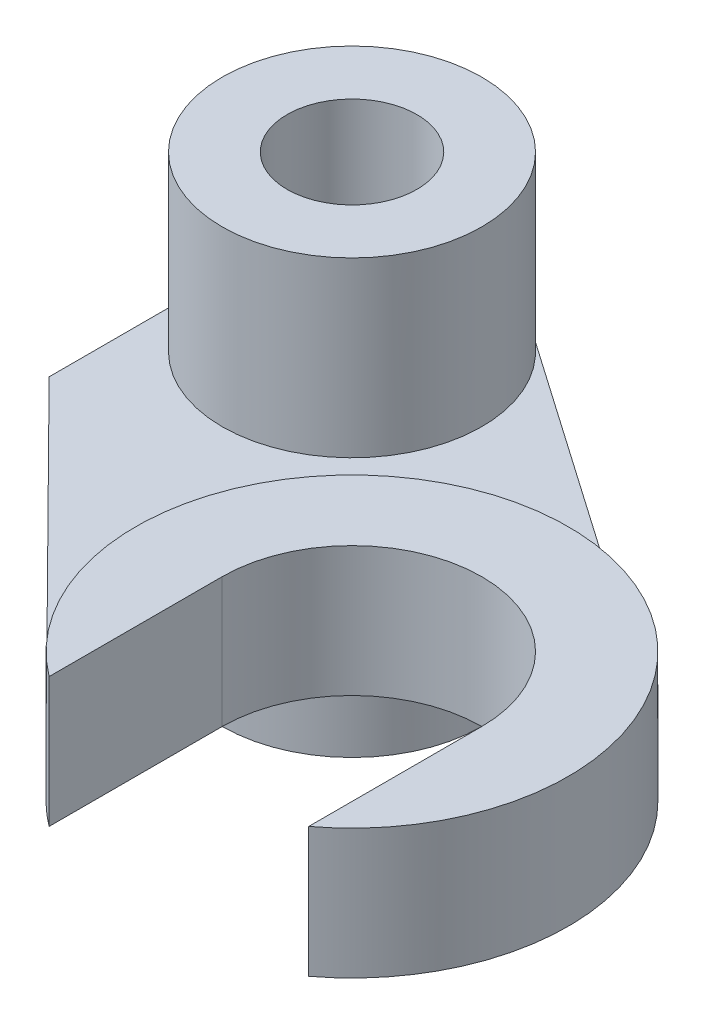
SolidWorks part; units mm, degrees
ref_plane "Front Plane" through (0, 0, 0) normal (0, 0, 1) x (1, 0, 0)
ref_plane "Top Plane" through (0, 0, 0) normal (0, 1, 0) x (1, 0, 0)
ref_plane "Right Plane" through (0, 0, 0) normal (1, 0, 0) x (0, 0, -1)
sketch "Sketch1" plane through (0, 0, 0) normal (0, 1, 0) x (1, 0, 0)
  line L0 (-30, 0) -> (-30, -40)
  line L1 (-30, -40) -> (44.4774, -115.1872)
  line L2 (17.1291, 24.6291) -> (108.5485, -38.9515)
  line L5 (50, -80) -> (50, -120)
  line L7 (110, -80) -> (110, -120)
  circle A0 centre (0, 0) radius 30
  circle A1 centre (0, 0) radius 15
  arc A2 (110, -80) -> (50, -80) centre (80, -80) ccw
  arc A3 (110, -120) -> (50, -120) centre (80, -80) ccw
  dimension "D1" = 60
  dimension "D2" = 30
  dimension "D3" = 80
  dimension "D5" = 60
  dimension "D6" = 100
  dimension "D4" = 80
  dimension "D7" = 40
extrude "Boss-Extrude1" add sketch "Sketch1" along normal blind 10 contours A0 A1 | A3 L2 A0 L0 L1 | L7 A3 L5 A2 region at (24.8601, 0, 38.1742) region at (-13.5017, 0, -25.8363) region at (42.7529, 0, 48.6962)
extrude "Boss-Extrude2" add sketch "Sketch1<3>" against normal blind 50 and the other way blind 50 contours A0 A1 region at (-13.5017, 0, -25.8363)
sketch "Sketch1<3>" plane through (0, 0, 0) normal (0, 1, 0) x (1, 0, 0) same geometry as "Sketch1"
extrude "Boss-Extrude3" add sketch "Sketch1<4>" along normal blind 30 contours L7 A3 L5 A2 region at (42.7529, 0, 48.6962)
sketch "Sketch1<4>" plane through (0, 0, 0) normal (0, 1, 0) x (1, 0, 0) same geometry as "Sketch1"
